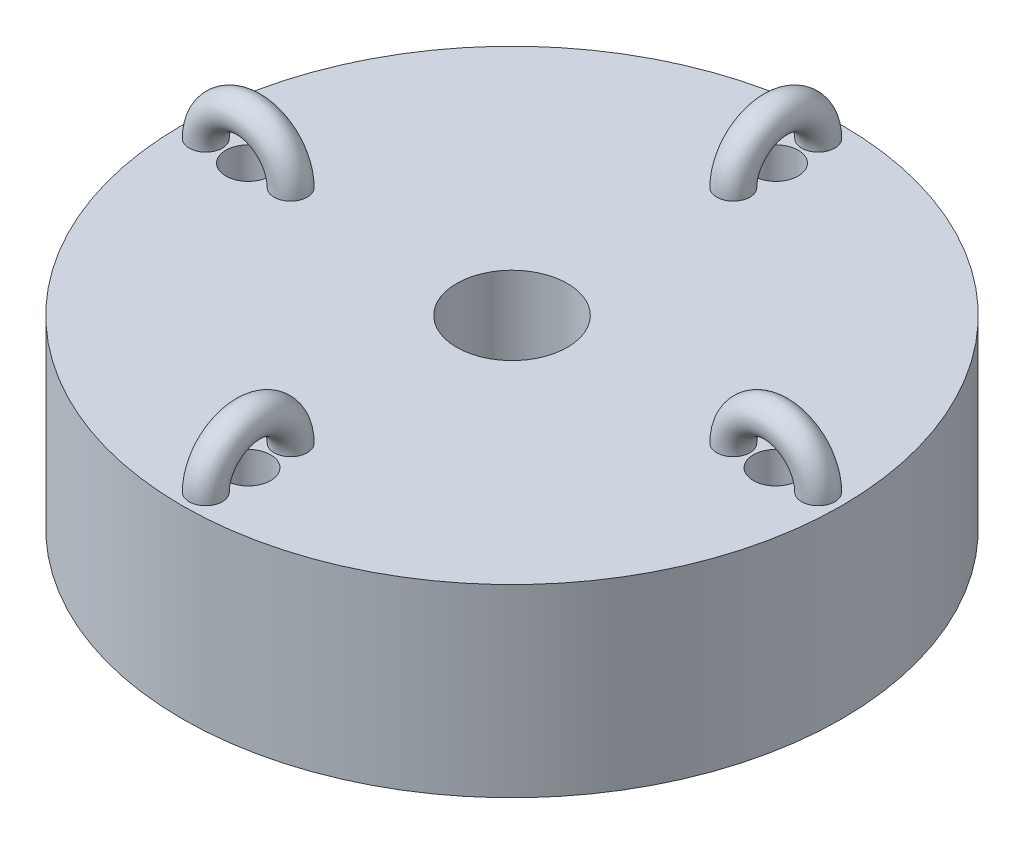
SolidWorks part; units mm, degrees
ref_plane "前视基准面" through (0, 0, 0) normal (0, 0, 1) x (1, 0, 0)
ref_plane "上视基准面" through (0, 0, 0) normal (0, 1, 0) x (1, 0, 0)
ref_plane "右视基准面" through (0, 0, 0) normal (1, 0, 0) x (0, 0, -1)
sketch "草图1" plane through (0, 0, 0) normal (0, 1, 0) x (1, 0, 0)
  circle A0 centre (0, 0) radius 12.5
  circle A1 centre (0, 0) radius 1
  circle A2 centre (0, 10) radius 0.85
  circle A3 centre (10, 0) radius 0.85
  circle A4 centre (0, -10) radius 0.85
  circle A5 centre (-10, 0) radius 0.85
  point P15 (0, 0)
  dimension "D1" = 2
  dimension "D2" = 1.7
  dimension "D5" = 25
  dimension "D4" = 10
  dimension "D3" = 4
extrude "凸台-拉伸1" add sketch "草图1" along normal blind 7
sketch "草图7" plane through (0, 0, 0) normal (0, 0, 1) x (1, 0, 0)
  line L0 (-9.15, 7) -> (-10.85, 7) construction
  line L1 (12.5, 7) -> (-12.5, 7) construction
  arc A0 (-8.3909, 7) -> (-11.6091, 7) centre (-10, 7) ccw
sketch "草图8" plane through (0, 7, 0) normal (0, 1, 0) x (1, 0, 0)
  circle A0 centre (-8.3909, 0) radius 0.6293
sweep "扫描2" add profiles "草图8" path "草图7"
ref_axis "基准轴1" through (0, 9.7003, 0) along (0, -1, 0)
pattern_circular "阵列(圆周)1" count 4 over 360 about axis through (0, 9.7003, 0) along (0, -1, 0) of "扫描2"
sketch "草图9" plane through (0, 7, 0) normal (0, 1, 0) x (1, 0, 0)
  circle A0 centre (0, 0) radius 2.1
  dimension "D1" = 4.2
extrude "切除-拉伸3" cut sketch "草图9" against normal blind 4
